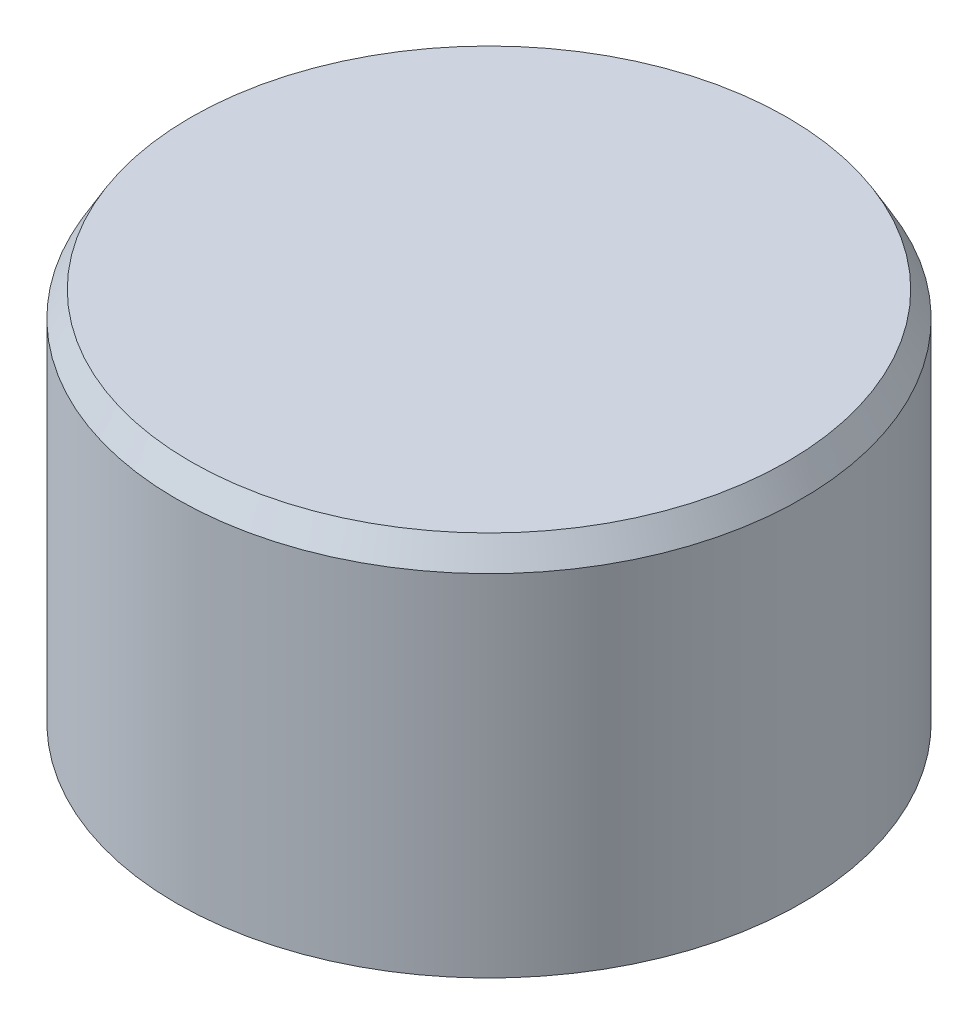
SolidWorks part; units mm, degrees
material "Калифорния"
ref_plane "Спереди" through (0, 0, 0) normal (0, 0, 1) x (1, 0, 0)
ref_plane "Сверху" through (0, 0, 0) normal (0, 1, 0) x (1, 0, 0)
ref_plane "Справа" through (0, 0, 0) normal (1, 0, 0) x (0, 0, -1)
sketch "Контур ручки" plane through (0, 0, 0) normal (0, 1, 0) x (1, 0, 0)
  circle A0 centre (0, 0) radius 12.5
  dimension "D1" = 25
extrude "Ручка" add sketch "Контур ручки" along normal blind 15
sketch "Эскиз крепежа" plane through (0, 0, 0) normal (0, 1, 0) x (1, 0, 0)
  circle A0 centre (0, 0) radius 10
  point P1 (9.8869, -1.651)
  dimension "D1" = 20
extrude "Крепёж" cut sketch "Эскиз крепежа" along normal blind 3
chamfer "Фаска1" distance 1 angle 30 1 edges at (0, 15, 12.5) first distance on face at (0, 15, 12.5)
sketch "Эскиз1" plane through (0, 0, 0) normal (0, 1, 0) x (1, 0, 0)
  circle A0 centre (0, 0) radius 1.5
  dimension "D1" = 3
extrude "Вырез-Вытянуть1" cut sketch "Эскиз1" along normal blind 8
